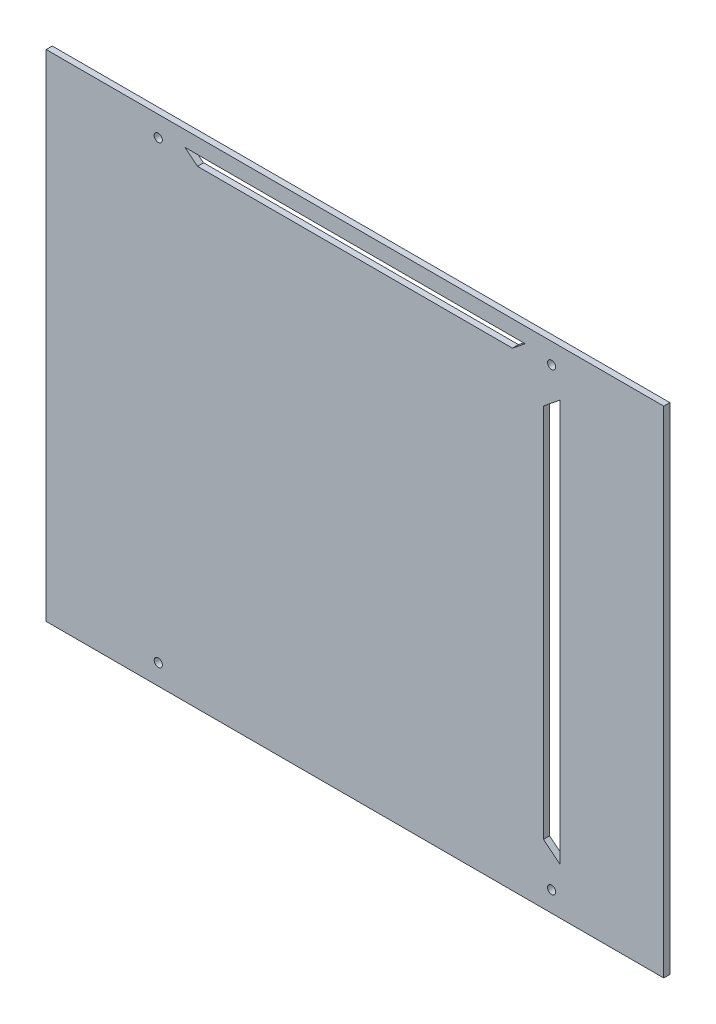
SolidWorks part; units mm, degrees
ref_plane "Front Plane" through (0, 0, 0) normal (0, 0, 1) x (1, 0, 0)
ref_plane "Top Plane" through (0, 0, 0) normal (0, 1, 0) x (1, 0, 0)
ref_plane "Right Plane" through (0, 0, 0) normal (1, 0, 0) x (0, 0, -1)
sketch "Sketch1" plane through (0, 0, 0) normal (0, 0, 1) x (1, 0, 0)
  line L0 (0, 0) -> (-206.9982, 0) construction
  line L1 (151.5, -121.5) -> (-151.5, -121.5)
  line L2 (151.5, -121.5) -> (151.5, 121.5)
  line L3 (151.5, 121.5) -> (-151.5, 121.5)
  line L4 (-151.5, -121.5) -> (-151.5, 121.5)
  line L5 (151.5, -121.5) -> (-151.5, 121.5) construction
  line L6 (151.5, 121.5) -> (-151.5, -121.5) construction
  line L7 (139.0309, -111.5) -> (-139.0309, -111.5) construction
  line L8 (139.0309, -111.5) -> (139.0309, 111.5) construction
  line L9 (139.0309, 111.5) -> (-139.0309, 111.5) construction
  line L10 (-139.0309, -111.5) -> (-139.0309, 111.5) construction
  line L11 (139.0309, -111.5) -> (-139.0309, 111.5) construction
  line L12 (139.0309, 111.5) -> (-139.0309, -111.5) construction
  line L13 (100.5, 98.5) -> (100.5, -98.5)
  line L14 (92.5, 92.0842) -> (92.5, -92.0842)
  line L15 (100.5, 98.5) -> (92.5, 92.0842)
  line L16 (100.5, -98.5) -> (92.5, -92.0842)
  line L17 (83.5, 114) -> (-83.5, 114)
  line L18 (96.5, 92.0842) -> (96.5, -92.0842) construction
  line L19 (-83.5, 114) -> (-77.2654, 109)
  line L20 (83.5, 114) -> (77.2654, 109)
  line L21 (139.0309, 114) -> (-139.0309, 114) construction
  line L22 (77.2654, 109) -> (-77.2654, 109)
  circle A0 centre (-96.5, 111.5) radius 2
  circle A1 centre (96.5, 111.5) radius 2
  circle A2 centre (96.5, -111.5) radius 2
  circle A3 centre (-96.5, -111.5) radius 2
  point P0 (0, 0)
  point P5 (0, 0)
  dimension "D4" = 4
  dimension "D5" = 4
  dimension "D1" = 303
  dimension "D2" = 243
  dimension "D3" = 10
  dimension "D6" = 55
  dimension "D7" = 55
  dimension "D8" = 13
  dimension "D9" = 8
  dimension "D10" = 55
  dimension "D11" = 13
  dimension "D14" = 13
  dimension "D15" = 13
  dimension "D13" = 2.5
  dimension "D12" = 2.5
  dimension "D16" = 4
extrude "Boss-Extrude1" add sketch "Sketch1" along normal blind 3
